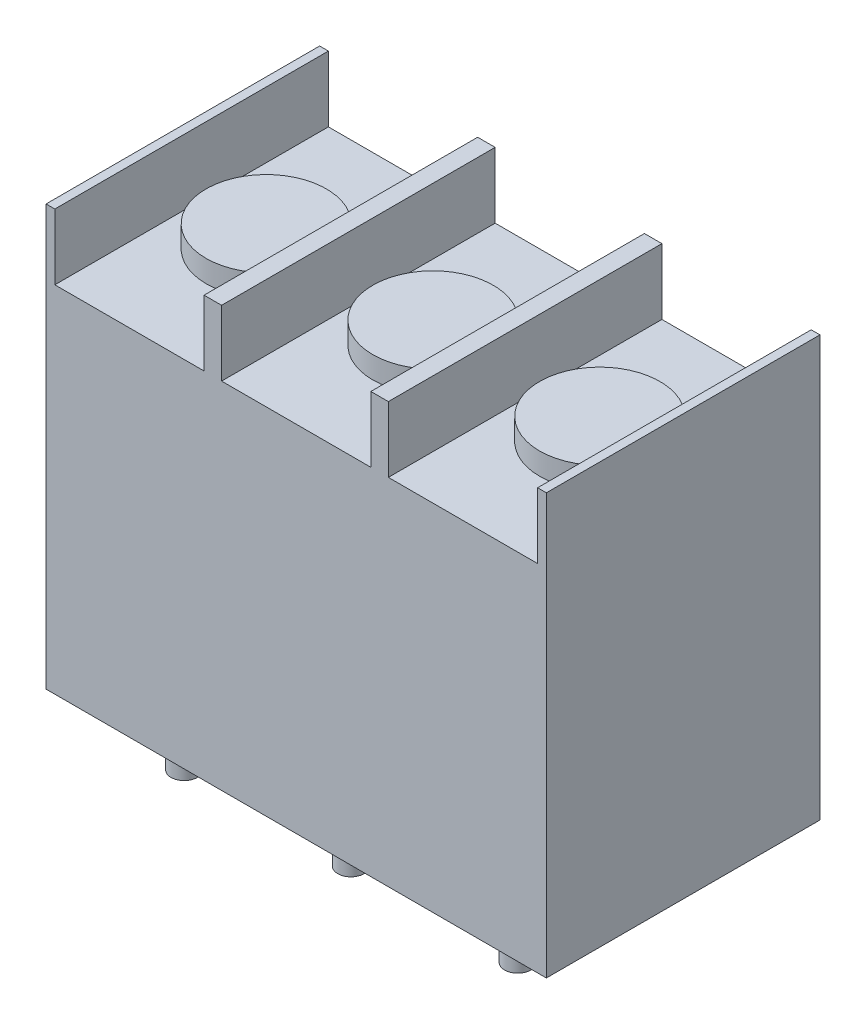
SolidWorks part; units mm, degrees
ref_plane "前视基准面" through (0, 0, 0) normal (0, 0, 1) x (1, 0, 0)
ref_plane "上视基准面" through (0, 0, 0) normal (0, 1, 0) x (1, 0, 0)
ref_plane "右视基准面" through (0, 0, 0) normal (1, 0, 0) x (0, 0, -1)
sketch "草图1" plane through (0, 0, 0) normal (0, 1, 0) x (1, 0, 0)
  line L0 (-11.1447, 0) -> (12.1543, 0) construction
  line L1 (-11.43, 6.25) -> (11.43, 6.25)
  line L2 (-11.43, 6.25) -> (-11.43, -6.25)
  line L3 (-11.43, -6.25) -> (11.43, -6.25)
  line L4 (11.43, 6.25) -> (11.43, -6.25)
  line L5 (0, 11.4931) -> (0, -8.9219) construction
  dimension "D1" = 22.86
  dimension "D2" = 12.5
extrude "拉伸1" add sketch "草图1" along normal blind 19.2
sketch "草图2" plane through (0, 19.2, 0) normal (0, 1, 0) x (-1, 0, 0)
  line L0 (0, 8.3959) -> (0, -7.6637) construction
  line L1 (11.43, 6.25) -> (-11.43, 6.25) construction
  line L2 (-11.03, 6.25) -> (-4.21, 6.25)
  line L3 (-11.03, 6.25) -> (-11.03, -6.25)
  line L4 (-11.03, -6.25) -> (-4.21, -6.25)
  line L5 (-4.21, 6.25) -> (-4.21, -6.25)
  line L6 (-11.43, -6.25) -> (11.43, -6.25) construction
  line L7 (-11.43, 6.25) -> (-11.43, -6.25) construction
  line L8 (-3.81, 8.3959) -> (-3.81, -7.4155) construction
  line L9 (-3.41, 6.25) -> (3.41, 6.25)
  line L10 (-3.41, 6.25) -> (-3.41, -6.25)
  line L11 (-3.41, -6.25) -> (3.41, -6.25)
  line L12 (3.41, 6.25) -> (3.41, -6.25)
  line L13 (4.21, 6.25) -> (11.03, 6.25)
  line L14 (4.21, 6.25) -> (4.21, -6.25)
  line L15 (4.21, -6.25) -> (11.03, -6.25)
  line L16 (11.03, 6.25) -> (11.03, -6.25)
  dimension "D1" = 0.4
  dimension "D2" = 3.81
  dimension "D3" = 0.4
extrude "切除-拉伸1" cut sketch "草图2" against normal blind 3
sketch "草图3" plane through (0, 0, 0) normal (0, -1, 0) x (1, 0, 0)
  line L0 (9.9189, 3.75) -> (-9.4712, 3.75) construction
  line L1 (0, -8.128) -> (0, 7.9902) construction
  circle A0 centre (0, 3.75) radius 0.6
  circle A1 centre (7.62, 3.75) radius 0.6
  circle A2 centre (-7.62, 3.75) radius 0.6
  dimension "D2" = 1.2
  dimension "D1" = 10
extrude "拉伸2" add sketch "草图3" along normal blind 2.54
sketch "草图4" plane through (0, 16.2, 0) normal (0, 1, 0) x (-1, 0, 0)
  circle A0 centre (0, 0) radius 2.75
  circle A1 centre (7.62, 0) radius 2.75
  circle A2 centre (-7.62, 0) radius 2.75
  dimension "D1" = 5.5
extrude "拉伸3" add sketch "草图4" along normal blind 1
